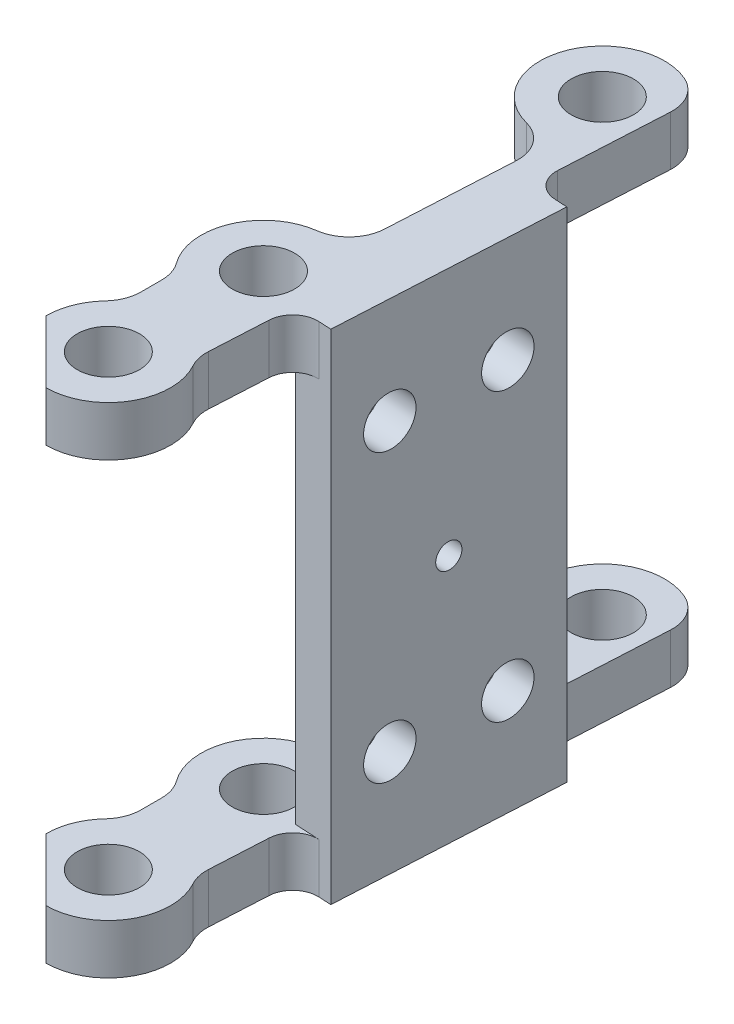
SolidWorks part; units mm, degrees
ref_plane "Front Plane" through (0, 0, 0) normal (0, 0, 1) x (1, 0, 0)
ref_plane "Top Plane" through (0, 0, 0) normal (0, 1, 0) x (1, 0, 0)
ref_plane "Right Plane" through (0, 0, 0) normal (1, 0, 0) x (0, 0, -1)
sketch "Sketch1" plane through (0, 0, 0) normal (0, 1, 0) x (1, 0, 0)
  line L0 (143.3333, 493) -> (716.6667, 493) construction
sketch "Sketch2" plane through (0, 0, 0) normal (0, 1, 0) x (1, 0, 0)
  line L0 (81.4722, 69.2986) -> (86.4722, 64.2986)
  line L1 (83.6263, 73.4096) -> (83.6263, 77.5229)
  line L2 (89.7299, 102.0349) -> (88.8636, 85.8025)
  line L7 (92.4509, 110.0003) -> (90.4247, 72.3609)
  line L8 (92.0481, 102.5189) -> (94.5466, 102.5189)
  line L9 (68.622, 64.6679) -> (68.8091, 64.6679)
  line L10 (82.0956, 50.9646) -> (82.0324, 51.0811)
  line L12 (94.5466, 102.5189) -> (93.4489, 82.1265)
  line L13 (94.0355, 93.0228) -> (93.4252, 81.6866)
  line L14 (93.4252, 81.6866) -> (90.9267, 81.6866)
  line L15 (47.4708, 107.3244) -> (47.5459, 107.4406)
  line L16 (50.5974, 103.1038) -> (50.7762, 103.3805)
  circle A0 centre (86.4722, 69.2986) radius 2.5
  arc A9 (88.8636, 85.8025) -> (83.6263, 77.5229) centre (87.0921, 81.1269) ccw
  arc A10 (83.6263, 73.4096) -> (81.4722, 69.2986) centre (86.4722, 69.2986) ccw
  arc A13 (92.4509, 110.0003) -> (89.7266, 101.9713) centre (88.5782, 106.8376) ccw
  arc A14 (86.4722, 64.2986) -> (90.4247, 72.3609) centre (86.4722, 69.2986) ccw
  circle A15 centre (87.0921, 81.1269) radius 2.5
  circle A18 centre (88.5782, 106.8376) radius 2.5
extrude "Boss-Extrude3" add sketch "Sketch2" along normal blind 4 contours L2 L7 A18 A15 A0 region at (82.4755, 0, -71.3928)
sketch "Sketch3" plane through (0, 4, 0) normal (0, 1, 0) x (1, 0, 0)
  line L0 (91.801, 97.9276) -> (90.8334, 79.9536)
  line L1 (91.801, 97.9276) -> (94.801, 97.7661)
  line L2 (90.8334, 79.9536) -> (93.8334, 79.7922)
  line L3 (94.801, 97.7661) -> (93.8334, 79.7922)
  line L4 (92.4509, 110.0003) -> (90.4247, 72.3609) construction
  dimension "D1" = 3
  dimension "D2" = 18
extrude "Boss-Extrude4" add sketch "Sketch3" against normal blind 40
ref_plane "Plane1" through (0, -16, 0) normal (0, 1, 0) x (1, 0, 0)
mirror "Mirror1" about plane through (0, -16, 0) normal (0, 1, 0) of "Boss-Extrude3"
fillet "Fillet1" radius 2 4 edges at (90.8334, -34, -79.9536) (90.8334, 2, -79.9536) (91.801, -34, -97.9276) (91.801, 2, -97.9276)
sketch "Sketch4" plane through (86.2794, 0, 4.6445) normal (-0.9986, 0, -0.0538) x (-0.0538, 0, 0.9986)
  line L0 (-84.7207, 0) -> (-89.2207, 0) construction
  line L1 (-102.7207, 0) -> (-84.7207, 0) construction
  line L2 (-89.2207, 0) -> (-89.2207, -4.5) construction
  line L3 (-93.7207, 0) -> (-93.7207, -7.4232) construction
  line L4 (-102.7207, -16) -> (-84.7207, -16) construction
  line L6 (-102.7207, -32) -> (-102.7207, 0) construction
  line L7 (-84.7207, -32) -> (-84.7207, 0) construction
  circle A0 centre (-89.2207, -4.5) radius 2
  circle A1 centre (-98.2207, -4.5) radius 2
  circle A2 centre (-89.2207, -27.5) radius 2
  circle A3 centre (-98.2207, -27.5) radius 2
  circle A4 centre (-93.7207, -16) radius 1
extrude "Cut-Extrude1" cut sketch "Sketch4" against normal blind 10
fillet "Fillet3" radius 3 10 edges at (92.4509, -34, -110.0003) (92.4509, 2, -110.0003) (90.4247, -34, -72.3609) (90.4247, 2, -72.3609) (89.7266, -34, -101.9713) (89.7266, 2, -101.9713) (83.6263, 2, -73.4096) (83.6263, 2, -77.5229) (83.6263, -34, -73.4096) (83.6263, -34, -77.5229)
fillet "Fillet4" radius 3 2 edges at (88.8636, -34, -85.8025) (88.8636, 2, -85.8025)
ref_plane "Plane2" through (5.0916, 0, -94.5837) normal (-0.0538, 0, 0.9986) x (0.9986, 0, 0.0538)
sketch "Sketch5" plane through (5.0916, 0, -94.5837) normal (-0.0538, 0, 0.9986) x (0.9986, 0, 0.0538)
  line L0 (86.4043, -32) -> (86.4043, 0) construction
  line L1 (86.4043, -6.8174) -> (86.4043, -16.0234)
  circle A0 centre (84.5501, -11.1421) radius 1.5
  arc A1 (84.5501, -9.1421) -> (84.5501, -13.1421) centre (84.5501, -11.1421) ccw
  spline S0 degree 3 poles (84.5501, -9.1421) (85.3763, -8.9966) (85.5964, -8.4523) (86.0299, -7.5374) (86.34, -7.1763) (86.4043, -6.8174) knots 0 0 0 0 0.605222 0.705222 1 1 1 1
  spline S1 degree 3 poles (84.5501, -13.1421) (85.1022, -13.2604) (85.6903, -14.2879) (86.2867, -15.3654) (86.4043, -16.0234) knots 0 0 0 0 0.420966 1 1 1 1
  point P2 (86.0989, -9.1543)
  dimension "D1" = 3
  dimension "D2" = 4
extrude "Boss-Extrude5" add sketch "Sketch5" along normal mid plane 5
